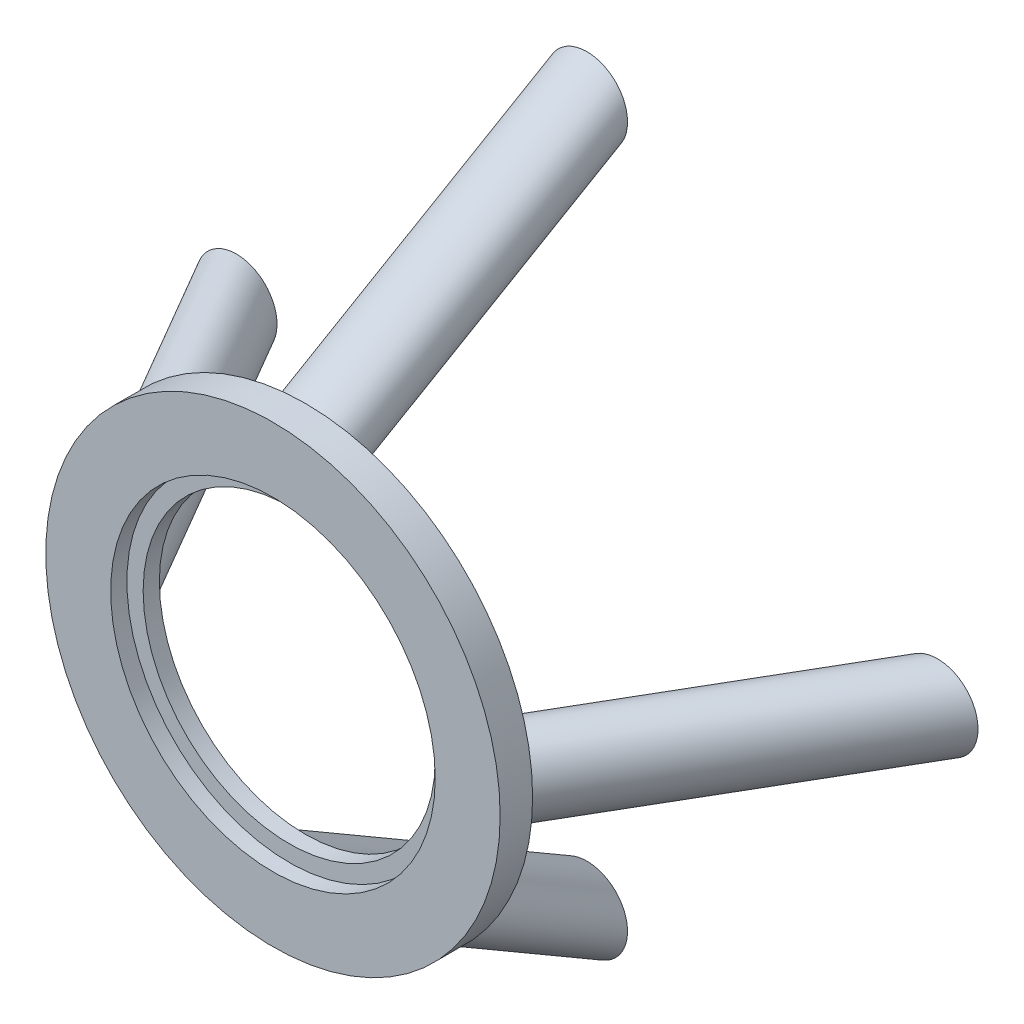
SolidWorks part; units mm, degrees
ref_plane "Front Plane" through (0, 0, 0) normal (0, 0, 1) x (1, 0, 0)
ref_plane "Top Plane" through (0, 0, 0) normal (0, 1, 0) x (1, 0, 0)
ref_plane "Right Plane" through (0, 0, 0) normal (1, 0, 0) x (0, 0, -1)
sketch "Sketch1" plane through (0, 0, 0) normal (0, 0, 1) x (1, 0, 0)
  circle A1 centre (0, 0) radius 70
  circle A2 centre (0, 0) radius 50
  circle A3 centre (0, 0) radius 45
  dimension "D1" = 5
extrude "Boss-Extrude1" add sketch "Sketch1" along normal blind 10 contours A2 | A1
extrude "Boss-Extrude3" add sketch "Sketch1<6>" along normal blind 5 contours A2 A3 region at (-48.5858, 0, 0)
sketch "Sketch1<6>" plane through (0, 0, 0) normal (0, 0, 1) x (1, 0, 0) same geometry as "Sketch1"
sketch "Sketch2" plane through (0, 0, 0) normal (0, 0, -1) x (-1, 0, 0)
  circle A0 centre (0, -57.5) radius 12.5
  circle A1 centre (0, 0) radius 70 construction
  circle A2 centre (0, 0) radius 45 construction
sketch "Sketch3" plane through (0, 0, 0) normal (1, 0, 0) x (0, 0, -1)
  line L1 (0, -70) -> (0, -45) construction
  line L2 (0, -57.5) -> (86.7319, -107.983)
  point P8 (0, -57.5)
sweep "Sweep1" add profiles "Sketch2" path "Sketch3"
pattern_circular "CirPattern2" count 4 over 360 about axis through (0, 0, 10) along (0, 0, -1) of "Sweep1"
